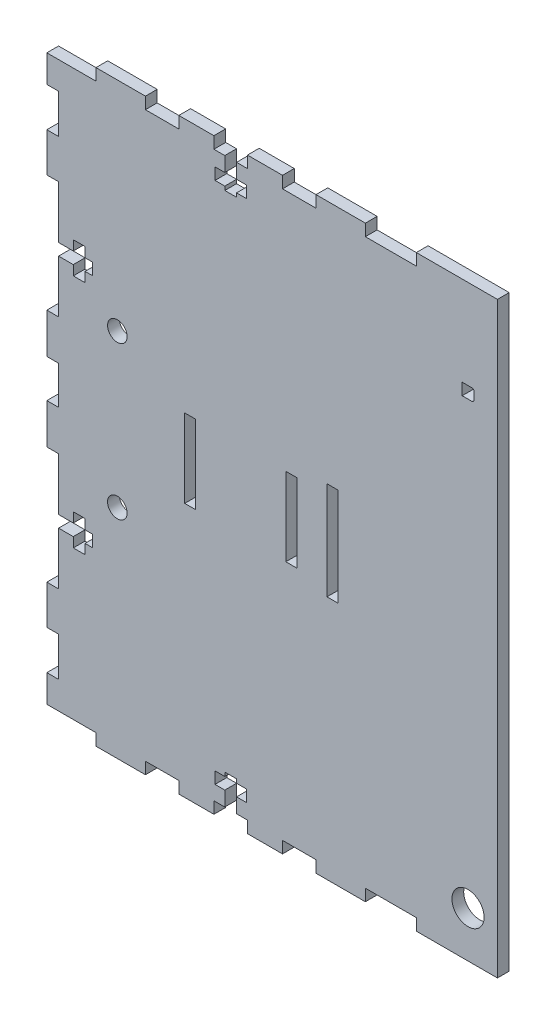
SolidWorks part; units mm, degrees
material "Balsa"
ref_plane "Alzado" through (0, 0, 0) normal (0, 0, 1) x (1, 0, 0)
ref_plane "Planta" through (0, 0, 0) normal (0, 1, 0) x (1, 0, 0)
ref_plane "Vista lateral" through (0, 0, 0) normal (1, 0, 0) x (0, 0, -1)
sketch "Croquis1" plane through (0, 0, 0) normal (0, 0, 1) x (1, 0, 0)
  line L0 (419.4017, 248.6372) -> (419.4017, 255.6372)
  line L1 (419.4017, 255.6372) -> (422.4017, 255.6372)
  line L2 (422.4017, 255.6372) -> (422.4017, 265.6372)
  line L3 (422.4017, 265.6372) -> (419.4017, 265.6372)
  line L4 (419.4017, 265.6372) -> (419.4017, 275.6372)
  line L5 (419.4017, 275.6372) -> (422.4017, 275.6372)
  line L6 (422.4017, 315.7622) -> (422.4017, 325.5122)
  line L7 (422.4017, 365.6372) -> (419.4017, 365.6372)
  line L8 (419.4017, 365.6372) -> (419.4017, 375.6372)
  line L9 (419.4017, 375.6372) -> (422.4017, 375.6372)
  line L10 (422.4017, 375.6372) -> (422.4017, 385.6372)
  line L11 (422.4017, 385.6372) -> (419.4017, 385.6372)
  line L12 (419.4017, 392.6372) -> (419.4017, 385.6372)
  line L13 (513.4018, 371.6372) -> (513.4018, 369.6372)
  line L14 (512.9018, 369.1372) -> (510.4018, 369.1372)
  line L15 (510.4018, 369.1372) -> (510.4018, 372.1372)
  line L16 (510.4018, 372.1372) -> (512.9018, 372.1372)
  line L52 (419.4017, 335.7622) -> (419.4017, 325.5122)
  line L53 (419.4017, 335.7622) -> (422.4017, 335.7622)
  line L54 (419.4017, 325.5122) -> (422.4017, 325.5122)
  line L55 (419.4017, 315.7622) -> (419.4017, 305.5122)
  line L56 (419.4017, 315.7622) -> (422.4017, 315.7622)
  line L57 (419.4017, 305.5122) -> (422.4017, 305.5122)
  line L58 (519.4017, 248.6371) -> (519.4017, 392.6373)
  line L59 (426.1513, 352.1994) -> (422.4017, 352.1994)
  line L60 (429.1517, 354.6999) -> (426.1513, 354.6999)
  line L61 (429.1517, 349.1994) -> (429.1517, 346.6994)
  line L62 (431.1017, 352.1994) -> (431.1017, 349.1994)
  line L63 (429.1517, 346.6994) -> (426.1513, 346.6994)
  line L64 (426.1513, 352.1994) -> (426.1513, 354.6999)
  line L65 (429.1517, 352.1994) -> (429.1517, 354.6999)
  line L66 (431.1017, 352.1994) -> (429.1517, 352.1994)
  line L67 (426.1513, 349.1994) -> (426.1513, 346.6994)
  line L68 (431.1017, 349.1994) -> (429.1517, 349.1994)
  line L69 (422.4017, 349.1994) -> (426.1513, 349.1994)
  line L70 (426.1513, 292.0744) -> (422.4017, 292.0744)
  line L71 (429.1517, 294.5749) -> (426.1513, 294.5749)
  line L72 (429.1517, 289.0744) -> (429.1517, 286.5744)
  line L73 (431.1017, 292.0744) -> (431.1017, 289.0744)
  line L74 (429.1517, 286.5744) -> (426.1513, 286.5744)
  line L75 (426.1513, 292.0744) -> (426.1513, 294.5749)
  line L76 (429.1517, 292.0744) -> (429.1517, 294.5749)
  line L77 (431.1017, 292.0744) -> (429.1517, 292.0744)
  line L78 (426.1513, 289.0744) -> (426.1513, 286.5744)
  line L79 (431.1017, 289.0744) -> (429.1517, 289.0744)
  line L80 (422.4017, 289.0744) -> (426.1513, 289.0744)
  line L81 (422.4017, 275.6372) -> (422.4017, 289.0744)
  line L82 (422.4017, 292.0744) -> (422.4017, 305.5122)
  line L83 (422.4017, 335.7622) -> (422.4017, 349.1994)
  line L84 (422.4017, 352.1994) -> (422.4017, 365.6372)
  line L85 (467.822, 252.3868) -> (467.822, 248.6371)
  line L86 (470.3224, 255.3871) -> (470.3224, 252.3868)
  line L87 (464.822, 255.3871) -> (462.322, 255.3871)
  line L88 (462.322, 255.3871) -> (462.322, 252.3868)
  line L89 (467.822, 252.3868) -> (470.3224, 252.3868)
  line L90 (467.822, 255.3871) -> (470.3224, 255.3871)
  line L91 (467.822, 256.3621) -> (467.822, 255.3871)
  line L92 (464.822, 252.3868) -> (462.322, 252.3868)
  line L93 (464.822, 256.3621) -> (464.822, 255.3871)
  line L94 (464.822, 248.6371) -> (464.822, 252.3868)
  line L95 (431.9403, 248.6372) -> (431.9403, 245.6372)
  line L96 (453.0923, 248.6371) -> (453.0923, 245.6371)
  line L97 (444.561, 245.6371) -> (444.561, 248.6371)
  line L98 (444.561, 248.6371) -> (453.0923, 248.6371)
  line L99 (444.561, 245.6371) -> (431.9403, 245.6372)
  line L100 (453.0923, 245.6371) -> (462.0423, 245.6371)
  line L101 (462.0423, 245.6371) -> (462.0423, 248.6371)
  line L103 (462.0423, 248.6371) -> (464.822, 248.6371)
  line L104 (467.822, 248.6371) -> (470.6017, 248.6371)
  line L105 (470.6017, 248.6371) -> (470.6017, 245.6371)
  line L106 (470.6017, 245.6371) -> (479.5517, 245.6371)
  line L107 (479.5517, 245.6371) -> (479.5517, 248.637)
  line L108 (479.5517, 248.637) -> (488.1017, 248.637)
  line L109 (488.1017, 248.637) -> (488.1017, 245.637)
  line L110 (500.7017, 245.637) -> (488.1017, 245.637)
  line L111 (500.7017, 245.637) -> (500.7017, 248.6371)
  line L112 (500.7017, 248.6371) -> (519.4017, 248.6371)
  line L113 (467.822, 256.3621) -> (464.822, 256.3621)
  line L114 (431.9403, 248.6372) -> (419.4017, 248.6372)
  line L115 (467.822, 388.8875) -> (467.822, 392.6372)
  line L116 (470.3224, 385.8872) -> (470.3224, 388.8875)
  line L117 (464.822, 385.8872) -> (462.322, 385.8872)
  line L118 (462.322, 385.8872) -> (462.322, 388.8875)
  line L119 (467.822, 388.8875) -> (470.3224, 388.8875)
  line L120 (467.822, 385.8872) -> (470.3224, 385.8872)
  line L121 (467.822, 384.9122) -> (467.822, 385.8872)
  line L122 (464.822, 388.8875) -> (462.322, 388.8875)
  line L123 (464.822, 384.9122) -> (464.822, 385.8872)
  line L124 (464.822, 392.6372) -> (464.822, 388.8875)
  line L125 (419.4017, 392.6372) -> (431.9403, 392.6372)
  line L126 (431.9403, 392.6372) -> (431.9403, 395.6372)
  line L127 (453.0923, 392.6372) -> (453.0923, 395.6372)
  line L128 (444.561, 395.6372) -> (444.561, 392.6372)
  line L129 (444.561, 392.6372) -> (453.0923, 392.6372)
  line L130 (444.561, 395.6372) -> (431.9403, 395.6372)
  line L131 (453.0923, 395.6372) -> (462.0423, 395.6372)
  line L132 (462.0423, 395.6372) -> (462.0423, 392.6372)
  line L133 (470.5017, 392.6372) -> (470.6017, 392.6372)
  line L134 (462.0423, 392.6372) -> (464.822, 392.6372)
  line L135 (467.822, 392.6372) -> (470.6017, 392.6372)
  line L136 (470.6017, 392.6372) -> (470.6017, 395.6372)
  line L137 (470.6017, 395.6372) -> (479.5517, 395.6372)
  line L138 (479.5517, 395.6372) -> (479.5517, 392.6373)
  line L139 (479.5517, 392.6373) -> (488.1017, 392.6373)
  line L140 (488.1017, 392.6373) -> (488.1017, 395.6373)
  line L141 (500.7017, 395.6373) -> (488.1017, 395.6373)
  line L142 (500.7017, 395.6373) -> (500.7017, 392.6373)
  line L143 (500.7017, 392.6373) -> (519.4017, 392.6373)
  line L144 (467.822, 384.9122) -> (464.822, 384.9122)
  arc A0 (512.9018, 369.1372) -> (513.4018, 369.6372) centre (512.9018, 369.6372) ccw
  arc A1 (513.4018, 371.6372) -> (512.9018, 372.1372) centre (512.9018, 371.6372) ccw
  arc A2 (509.3472, 259.8441) -> (513.4018, 252.8214) centre (511.9018, 256.6372) ccw
  arc A3 (514.4566, 253.4305) -> (510.4018, 260.4529) centre (511.9018, 256.6372) ccw
  circle A4 centre (511.9018, 256.6372) radius 4.1
extrude "Saliente-Extruir1" add sketch "Croquis1" along normal mid plane 3 contours L121 L144 L123 L117 L118 L122 L124 L134 L132 L131 L127 L129 L128 L130 L126 L125 L12 L11 L10 L9 L8 L7 L84 L59 L64 L60 L65 L66 L62 L68 L61 L63 L67 L69 L83 L53 L52 L54 L6 L56 L55 L57 L82 L70 L75 L71 L76 L77 L73 L79 L72 | A3 A4 A2 | L13 A1 L16 L15 L14 A0 region at (470.3413, 320.8443, 0) region at (511.885, 370.6372, 0) region at (511.9018, 256.6372, 0)
sketch "Croquis2" plane through (0, 0, 1.5) normal (0, 0, 1) x (1, 0, 0)
  line L0 (499.9018, 248.6371) -> (499.9018, 256.5572) construction
  line L3 (495.9018, 320.6372) -> (497.4017, 320.6372) construction
  line L4 (-506.5983, 320.6372) -> (485.2217, 320.6372) construction
  line L25 (470.9017, 407.8404) -> (470.9017, 229.2607) construction
  line L26 (422.4017, 315.7622) -> (422.4017, 325.5122) construction
  line L27 (422.4017, 292.0744) -> (422.4017, 305.5122) construction
  line L28 (457.4017, 272.1372) -> (480.4017, 272.1372) construction
  line L29 (457.4017, 272.1372) -> (457.4017, 369.1372) construction
  line L30 (457.4017, 369.1372) -> (480.4017, 369.1372) construction
  line L31 (480.4017, 272.1372) -> (480.4017, 369.1372) construction
  line L32 (457.4017, 272.1372) -> (480.4017, 369.1372) construction
  line L33 (457.4017, 369.1372) -> (480.4017, 272.1372) construction
  line L34 (468.9017, 379.2213) -> (468.9017, 256.6206) construction
  line L43 (480.4017, 330.6372) -> (483.2017, 330.6372)
  line L60 (457.4017, 330.6372) -> (454.6017, 330.6372)
  line L61 (457.4017, 330.6372) -> (457.4017, 310.6372)
  line L62 (457.4017, 310.6372) -> (454.6017, 310.6372)
  line L63 (454.6017, 330.6372) -> (454.6017, 310.6372)
  line L64 (480.4017, 330.6372) -> (480.4017, 310.6372)
  line L65 (480.4017, 310.6372) -> (483.2017, 310.6372)
  line L66 (483.2017, 330.6372) -> (483.2017, 310.6372)
  line L91 (500.7017, 248.6371) -> (519.4017, 248.6371) construction
  line L94 (495.9018, 320.6372) -> (497.4017, 320.6372) construction
  line L95 (500.7017, 392.6373) -> (519.4017, 392.6373) construction
  line L96 (497.4017, 320.6372) -> (495.9018, 320.6372) construction
  line L97 (519.4017, 320.6372) -> (503.9018, 320.6372) construction
  line L98 (519.4017, 248.6371) -> (519.4017, 392.6373) construction
  line L99 (499.9018, 272.7172) -> (499.9018, 284.5572) construction
  line L109 (499.9018, 312.5572) -> (499.9018, 316.5572) construction
  line L113 (499.9018, 389.0828) -> (499.9018, 392.6373) construction
  line L114 (422.4017, 335.7622) -> (422.4017, 349.1994) construction
  circle A2 centre (417.9017, 320.6372) radius 2.5 construction
  circle A3 centre (456.9017, 320.6372) radius 2.5 construction
  circle A25 centre (437.4017, 320.6372) radius 3.9521 construction
  circle A26 centre (437.4017, 340.1372) radius 2.5
  circle A27 centre (456.9017, 320.6372) radius 2.5
  circle A28 centre (437.4017, 301.1372) radius 2.5
  point P12 (503.4827, 320.6372)
  point P15 (437.4017, 320.6372)
  point P32 (468.9017, 320.6372)
  point P47 (456.0017, 330.6372)
  point P53 (437.4017, 320.6372)
  dimension "D7" = 5
  dimension "D20" = 5
  dimension "D4" = 12
  dimension "D3" = 19.5
  dimension "D5" = 4
  dimension "D8" = 48.5
  dimension "D9" = 97
  dimension "D10" = 23
  dimension "D11" = 35
  dimension "D12" = 20
  dimension "D13" = 2.8
  dimension "D14" = 0
  dimension "D18" = 39
  dimension "5" = 10
  dimension "D6" = 15
extrude "Cortar-Extruir1" cut sketch "Croquis2" against normal blind 11 contours L66 L43 L64 L65 | A3 | A2 | L61 L62 L63 L60 | A28 | A26 region at (481.8017, 320.6372, 1.5)
sketch "Croquis4" plane through (0, 0, -1.5) normal (0, 0, -1) x (-1, 0, 0)
  line L0 (-519.4017, 320.6372) -> (-422.4017, 320.6372) construction
  line L1 (-493.7017, 333.1372) -> (-490.9017, 333.1372)
  line L2 (-493.7017, 333.1372) -> (-493.7017, 308.1372)
  line L3 (-493.7017, 308.1372) -> (-490.9017, 308.1372)
  line L4 (-490.9017, 333.1372) -> (-490.9017, 308.1372)
  line L5 (-519.4017, 248.6371) -> (-519.4017, 392.6373) construction
  line L6 (-422.4017, 315.7622) -> (-422.4017, 325.5122) construction
  point P4 (-470.9017, 320.6372)
  dimension "D1" = 25
  dimension "D2" = 12.5
  dimension "D3" = 2.8
  dimension "D4" = 20
extrude "Cortar-Extruir3" cut sketch "Croquis4" against normal blind 13
sketch "Croquis5" plane through (519.4017, 0, 0) normal (1, 0, 0) x (0, 0, -1)
  line L4 (1.5, 248.6371) -> (1.5, 392.6373)
  line L5 (1.5, 392.6373) -> (-1.5, 392.6373)
  line L6 (-1.5, 392.6373) -> (-1.5, 248.6371)
  line L7 (-1.5, 248.6371) -> (1.5, 248.6371)
  line L8 (1.5, 248.6371) -> (1.5, 392.6373)
  line L9 (1.5, 392.6373) -> (-1.5, 392.6373)
  line L10 (-1.5, 392.6373) -> (-1.5, 248.6371)
  line L11 (-1.5, 248.6371) -> (1.5, 248.6371)
  dimension "D1" = 0
extrude "Saliente-Extruir2" add sketch "Croquis5" along normal blind 15
sketch "Croquis6" plane through (0, 0, 1.5) normal (0, 0, 1) x (1, 0, 0)
  line L0 (526.9017, 257.3371) -> (526.9017, 369.8371) construction
  line L1 (500.7017, 248.6371) -> (534.4017, 248.6371) construction
  line L2 (534.4017, 392.6373) -> (534.4017, 248.6371) construction
  line L3 (525.4017, 371.3371) -> (528.4017, 371.3371) construction
  line L4 (525.4017, 369.8371) -> (527.9017, 369.8371)
  line L5 (525.4017, 369.8371) -> (525.4017, 372.8371)
  line L6 (525.4017, 372.8371) -> (527.9017, 372.8371)
  line L7 (528.4017, 370.3371) -> (528.4017, 372.3371)
  circle A0 centre (526.9017, 257.3371) radius 4.1
  arc A1 (527.9017, 369.8371) -> (528.4017, 370.3371) centre (527.9017, 370.3371) ccw
  arc A2 (527.9017, 372.8371) -> (528.4017, 372.3371) centre (527.9017, 372.3371) cw
  point P16 (528.4017, 371.3371)
  point P18 (528.4017, 372.8371)
  dimension "D2" = 8.7
  dimension "D3" = 7.5
  dimension "D9" = 0.5
  dimension "D10" = 8.2
  dimension "D1" = 112.5
  dimension "D4" = 3
  dimension "D5" = 1.5
  dimension "D6" = 3
  dimension "D7" = 0
  dimension "D8" = 3
extrude "Cortar-Extruir4" cut sketch "Croquis6" against normal blind 15
sketch "Croquis7" plane through (0, 248.6371, 0) normal (0, -1, 0) x (1, 0, 0)
  line L0 (500.7017, 1.5) -> (534.4017, 1.5) construction
  line L1 (513.7017, 1.5) -> (534.4017, 1.5)
  line L2 (513.7017, 1.5) -> (513.7017, -1.5)
  line L3 (513.7017, -1.5) -> (534.4017, -1.5)
  line L4 (534.4017, 1.5) -> (534.4017, -1.5)
  line L5 (500.7017, -1.5) -> (534.4017, -1.5) construction
  line L6 (500.7017, 1.5) -> (500.7017, -1.5) construction
  line L7 (500.7017, -1.5) -> (534.4017, -1.5) construction
  line L8 (534.4017, -1.5) -> (534.4017, 1.5) construction
  point P10 (534.4017, -1.5)
  dimension "D1" = 13
extrude "Saliente-Extruir3" add sketch "Croquis7" along normal blind 3
sketch "Croquis8" plane through (0, 392.6373, 0) normal (0, 1, 0) x (1, 0, 0)
  line L0 (500.7017, -1.5) -> (534.4017, -1.5) construction
  line L1 (513.7017, -1.5) -> (534.4017, -1.5)
  line L2 (513.7017, -1.5) -> (513.7017, 1.5)
  line L3 (513.7017, 1.5) -> (534.4017, 1.5)
  line L4 (534.4017, -1.5) -> (534.4017, 1.5)
  line L5 (500.7017, 1.5) -> (534.4017, 1.5) construction
  line L6 (500.7017, -1.5) -> (500.7017, 1.5) construction
  point P10 (534.4017, 1.5)
  dimension "D1" = 13
extrude "Saliente-Extruir4" add sketch "Croquis8" along normal blind 3
